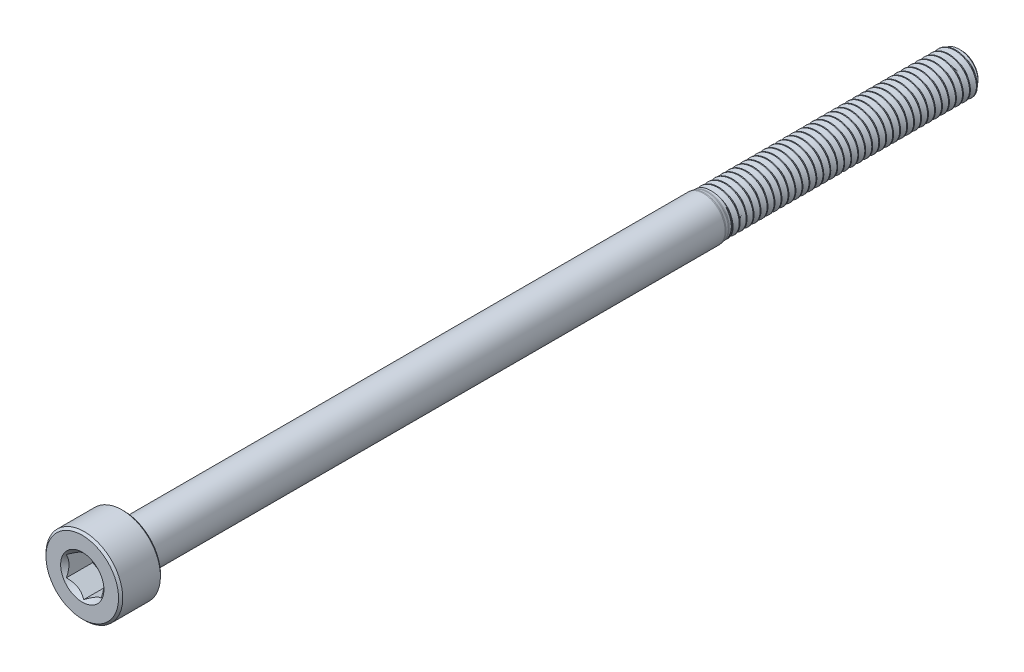
SolidWorks part; units mm, degrees
ref_plane "Front Plane" through (0, 0, 0) normal (0, 0, 1) x (1, 0, 0)
ref_plane "Top Plane" through (0, 0, 0) normal (0, 1, 0) x (1, 0, 0)
ref_plane "Right Plane" through (0, 0, 0) normal (1, 0, 0) x (0, 0, -1)
sketch "Sketch1" plane through (0, 0, 0) normal (1, 0, 0) x (0, 0, -1)
  line L0 (-31.5, 0) -> (31.5, 0) construction
  line L1 (31.5, 0) -> (31.5, 1.1752) construction
  line L2 (31.5, 1.1752) -> (31.1752, 1.5) construction
  line L3 (31.1752, 1.5) -> (31.125, 1.5) construction
  line L4 (31.125, 1.5) -> (-28.5, 1.5) construction
  line L5 (-28.5, 1.5) -> (-28.5, 2.75) construction
  line L6 (-28.5, 2.75) -> (-31.5, 2.75) construction
  line L7 (-31.5, 2.75) -> (-31.5, 0) construction
  line L8 (31.5, 1.1752) -> (31.5, 1.5) construction
  line L9 (31.4688, 1.5541) -> (31.7188, 1.1211) construction
  line L10 (31.7188, 1.1211) -> (31.9688, 1.5541) construction
  line L11 (31.9688, 1.5541) -> (31.4688, 1.5541) construction
  line L12 (31.7188, 1.5541) -> (31.7187, 1.5) construction
  line L13 (31.7188, 1.1211) -> (31.7188, 1.1752) construction
  line L14 (31.6875, 1.1752) -> (31.75, 1.1752) construction
  line L15 (31.5, 1.5) -> (31.9375, 1.5) construction
  line L16 (31.4844, 1.5271) -> (31.9531, 1.5271) construction
  line L17 (31.5, 0) -> (31.5, -1.5) construction
  line L18 (-28.65, 2.75) -> (-28.5, 2.6) construction
  line L19 (-31.35, 2.75) -> (-31.5, 2.6) construction
  line L20 (-28.5, 1.5) -> (-28.5, 0) construction
  line L21 (-28.5, 0.75) -> (-8.5, 0.75) construction
  line L22 (-8.5, 0.75) -> (11.5, 0.75) construction
  line L23 (11.5, 0.75) -> (31.5, 0.75) construction
  line L24 (-8.5, 0.75) -> (-8.5, 1.5) construction
  line L25 (-8.5, 1.5) -> (-8.5, 2.75) construction
  line L26 (11.5, 0.75) -> (11.5, 2.75) construction
  point P0 (-31.5, 1.25)
  point P3 (30.25, 1.5)
  point P4 (0, 0)
  point P18 (11.5, 1.5)
  point P22 (31.7188, 1.1752)
  point P24 (31.125, 1.5)
  point P25 (31.7187, 1.5)
  point P28 (31.7188, 1.5271)
  point P29 (30.25, -1.5)
  point P30 (-8.5, 1.5)
  point P31 (-30, 2.75)
  point P37 (-29.025, 2.75)
  point P38 (-31.275, 2.75)
  point P45 (-8.5, 0.75)
  point P46 (11.5, 0.75)
  point P49 (13.5, 1.5)
  dimension "D1" = 45
  dimension "D2" = 0.0625
  dimension "D7" = 0.15
  dimension "D8" = 0.15
  dimension "D9" = 0.15
  dimension "D10" = 0.075
  dimension "D11" = 0.375
  dimension "Drive Size" = 2.5
  dimension "Head Diameter" = 5.5
  dimension "Head Height" = 3
  dimension "Thread Pitch" = 0.5
  dimension "Thread Dia" = 3
  dimension "Length" = 60
  dimension "D12" = 0.375
  dimension "D4" = 1.25
  dimension "Minimum Thread Length" = 18
  dimension "D3" = 42
sketch "Sketch2" plane through (0, 0, 0) normal (1, 0, 0) x (0, 0, -1)
  line L0 (-31.5, 0) -> (-31.5, 2.6)
  line L1 (-31.35, 2.75) -> (-28.65, 2.75)
  line L2 (-28.5, 2.6) -> (-28.5, 1.7041)
  line L4 (31.1752, 1.5) -> (31.5, 1.1752)
  line L5 (31.5, 1.1752) -> (31.5, 0)
  line L6 (-28.5, 2.75) -> (-31.5, 2.75) construction
  line L7 (31.5, 0) -> (-31.5, 0)
  line L8 (-31.35, 2.75) -> (-31.5, 2.6) construction
  line L10 (-31.35, 2.75) -> (-31.5, 2.6)
  line L14 (-28.65, 2.75) -> (-28.5, 2.6) construction
  line L16 (-28.65, 2.75) -> (-28.5, 2.6)
  line L17 (-28.5, 1.5) -> (-28.5, 2.75) construction
  line L18 (-28.35, 1.5541) -> (13.0035, 1.5541)
  line L19 (13.3494, 1.5) -> (31.1752, 1.5)
  line L20 (31.125, 1.5) -> (-28.5, 1.5) construction
  line L21 (13.0766, 1.5469) -> (13.2763, 1.5072)
  line L22 (31.9688, 1.5541) -> (31.4688, 1.5541) construction
  arc A1 (-28.5, 1.7041) -> (-28.35, 1.5541) centre (-28.35, 1.7041) ccw
  arc A2 (13.0035, 1.5541) -> (13.0766, 1.5469) centre (13.0035, 1.1791) cw
  arc A3 (13.2763, 1.5072) -> (13.3494, 1.5) centre (13.3494, 1.875) ccw
  point P39 (13.3125, 1.5)
  dimension "D3" = 0.15
  dimension "D6" = 0.375
  dimension "D4" = 11.25
  dimension "D5" = 0.1875
revolve "Revolve1" add sketch "Sketch2" angle 360 about L7
sketch "Sketch3" plane through (0, 0, 31.5) normal (0, 0, 1) x (1, 0, 0)
  line L1 (1.25, -0.7217) -> (1.25, 0.7217)
  line L2 (1.25, 0.7217) -> (0, 1.4434)
  line L3 (0, 1.4434) -> (-1.25, 0.7217)
  line L4 (-1.25, 0.7217) -> (-1.25, -0.7217)
  line L5 (-1.25, -0.7217) -> (0, -1.4434)
  line L6 (0, -1.4434) -> (1.25, -0.7217)
  circle A0 centre (0, 0) radius 1.25 construction
  circle A1 centre (0, 0) radius 2.75 construction
  circle A2 centre (0, 0) radius 2.75 construction
  circle A3 centre (0, 0) radius 1.4434 construction
  dimension "D1" = 2.8868
extrude "Cut-Extrude1" cut sketch "Sketch3" against normal offset from surface (2 mm away) 1 up to face at (0, 2.6, 28.5)
sketch "Sketch4" plane through (0, 0, 31.5) normal (0, 0, 1) x (1, 0, 0)
  circle A0 centre (0, 0) radius 1.5516
  dimension "D1" = 3.1033
extrude "Cut-Extrude2" cut sketch "Sketch4" against normal up to vertex (1.5 mm away) draft 45 up to point (0, 2.75, 30)
sketch "Sketch11" plane through (0, 0, 0) normal (1, 0, 0) x (0, 0, -1)
  line L0 (-31.5, 0) -> (31.5, 0) construction
  line L1 (-31.5, 0) -> (31.5, 0) construction
  line L2 (-24.825, 0) -> (-24.825, 1.5) construction
  line L3 (31.125, 1.5) -> (-28.5, 1.5) construction
  line L4 (9.3285, 0) -> (9.3285, 1.5) construction
  point P2 (-24.825, 0)
  point P3 (9.3285, 0)
  dimension "D1" = 3.675
  dimension "D2" = 3.675
sketch "Sketch6" plane through (0, 0, -31.5) normal (0, 0, -1) x (-1, 0, 0)
  circle A0 centre (0, 0) radius 1.5
curve "Helix/Spiral1" pitch 0.5 height 18.5 radius 1.5 centre (0, 0, -31.5) axis (0, 0, 1) start towards (0, 1, 0)
sketch "Sketch10" plane through (0, 0, 0) normal (1, 0, 0) x (0, 0, -1)
  line L0 (13.5, -1.5) -> (13.5, 1.5)
  line L2 (-31.5, 0) -> (31.5, 0) construction
  point P3 (13.5, 0)
split "Split1" trim tools "Sketch10" bodies to split 106 resulting bodies 114 115
sketch "Sketch7" plane through (0, 0, 0) normal (1, 0, 0) x (0, 0, -1)
  line L0 (31.4844, 1.5271) -> (31.9531, 1.5271)
  line L1 (31.9531, 1.5271) -> (31.75, 1.1752)
  line L2 (31.75, 1.1752) -> (31.6875, 1.1752)
  line L3 (31.6875, 1.1752) -> (31.4844, 1.5271)
sweep "Cut-Sweep1" cut profiles "Sketch7" path "Helix/Spiral1" align with end faces yes
sketch "Sketch8" plane through (0, 0, 0) normal (1, 0, 0) x (0, 0, -1)
  line L0 (-28.5, 0) -> (-28.5, 1.5)
  line L2 (-28.5, 1.5) -> (13.5, 1.5)
  line L4 (13.5, 1.5) -> (14.366, 0)
  line L5 (14.366, 0) -> (-28.5, 0)
  line L6 (31.125, 1.5) -> (-28.5, 1.5) construction
  line L7 (-31.5, 0) -> (31.5, 0) construction
  dimension "D1" = 60
  dimension "D2" = 18
revolve "Revolve2" add sketch "Sketch8" angle 360 about L5
equation "\"D2@Sketch1\" = \"Thread Pitch@Sketch1\" / 8"
equation "\"D4@Helix/Spiral1\" = \"Thread Pitch@Sketch1\""
equation "\"D7@Sketch1\" = \"Head Height@Sketch1\" * .05"
equation "\"D8@Sketch1\"=\"D7@Sketch1\""
equation "\"D9@Sketch1\"=\"D7@Sketch1\""
equation "\"D10@Sketch1\"=\"D7@Sketch1\"/2"
equation "\"D11@Sketch1\"=\"D10@Sketch1\"*5"
equation "\"D4@Sketch1\"=\"Thread Pitch@Sketch1\"*2.5"
equation "\"D12@Sketch1\"=\"Thread Pitch@Sketch1\"*.75"
equation "\"D3@Helix/Spiral1\"=\"Minimum Thread Length@Sketch1\"+\"Thread Pitch@Sketch1\""
equation "\"D2@Sketch8\"=\"Minimum Thread Length@Sketch1\""
equation "\"D3@Sketch2\"=\"Thread Dia@Sketch1\"*0.05"
equation "\"D5@Sketch2\"=\"D12@Sketch1\"*0.5"
equation "\"D6@Sketch2\"=\"Thread Dia@Sketch1\"*0.125"
equation "\"D1@Sketch11\"=\"D3@Sketch1\"*0.0875"
equation "\"D2@Sketch11\"=\"D1@Sketch11\""
equation "\"D1@Sketch4\"=\"D1@Sketch3\"*1.075"
